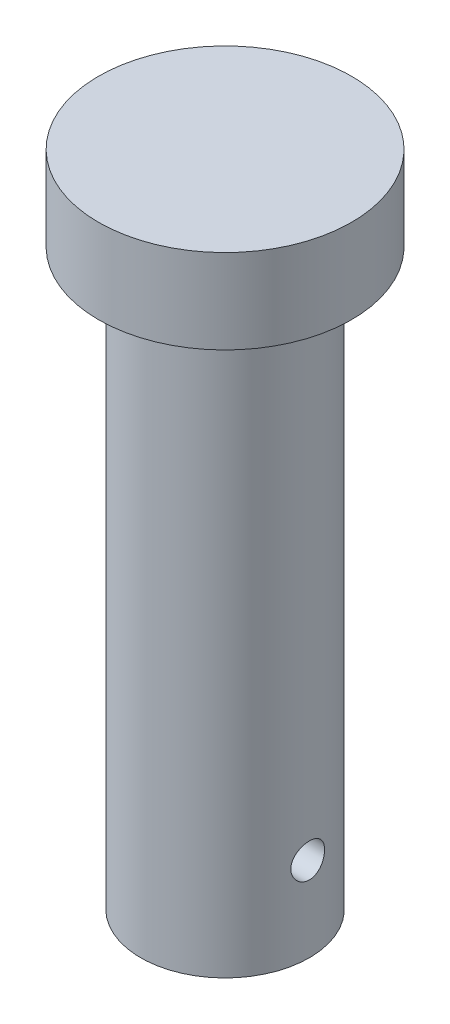
SolidWorks part; units mm, degrees
ref_plane "Front Plane" through (0, 0, 0) normal (0, 0, 1) x (1, 0, 0)
ref_plane "Top Plane" through (0, 0, 0) normal (0, 1, 0) x (1, 0, 0)
ref_plane "Right Plane" through (0, 0, 0) normal (1, 0, 0) x (0, 0, -1)
sketch "Sketch1" plane through (0, 0, 0) normal (0, 1, 0) x (1, 0, 0)
  circle A0 centre (0, 0) radius 22.5
  dimension "D1" = 45
extrude "Boss-Extrude1" add sketch "Sketch1" against normal blind 15
sketch "Sketch2" plane through (0, -15, 0) normal (0, -1, 0) x (1, 0, 0)
  circle A0 centre (0, 0) radius 15
  dimension "D1" = 30
extrude "Boss-Extrude2" add sketch "Sketch2" along normal blind 102
sketch "Sketch3" plane through (0, 0, 0) normal (1, 0, 0) x (0, 0, -1)
  line L0 (-15, -117) -> (15, -117) construction
  circle A0 centre (0, -102) radius 3
  dimension "D1" = 6
  dimension "D2" = 15
extrude "Cut-Extrude1" cut sketch "Sketch3" along normal through all and the other way blind 31
